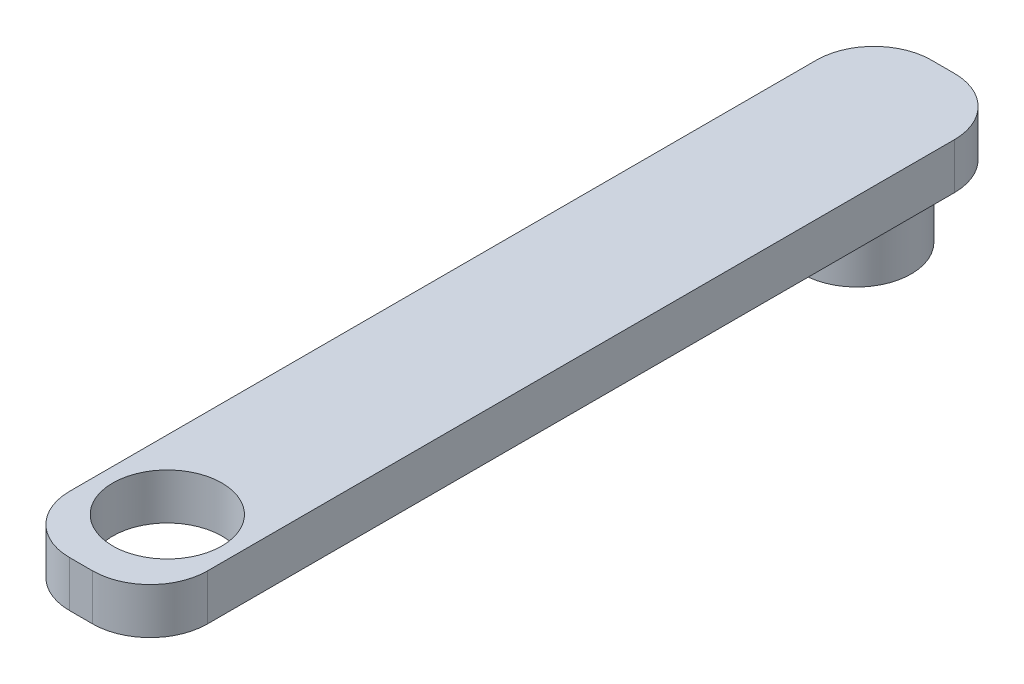
SolidWorks part; units mm, degrees
ref_plane "Front Plane" through (0, 0, 0) normal (0, 0, 1) x (1, 0, 0)
ref_plane "Top Plane" through (0, 0, 0) normal (0, 1, 0) x (1, 0, 0)
ref_plane "Right Plane" through (0, 0, 0) normal (1, 0, 0) x (0, 0, -1)
sketch "Sketch2" plane through (0, 0, 0) normal (0, 1, 0) x (1, 0, 0)
  line L0 (-55, 0) -> (55, 0) construction
  line L1 (-1, -37.5) -> (1, -37.5)
  line L2 (-6, -32.5) -> (-6, 32.5)
  line L3 (-1, 37.5) -> (1, 37.5)
  line L4 (6, -32.5) -> (6, 32.5)
  line L5 (-6, -37.5) -> (6, 37.5) construction
  line L6 (-6, 37.5) -> (6, -37.5) construction
  arc A0 (-1, -37.5) -> (-6, -32.5) centre (-1, -32.5) cw
  arc A1 (-1, 37.5) -> (-6, 32.5) centre (-1, 32.5) ccw
  arc A2 (1, -37.5) -> (6, -32.5) centre (1, -32.5) ccw
  arc A3 (6, 32.5) -> (1, 37.5) centre (1, 32.5) ccw
  circle A4 centre (0, 30) radius 4.75
  circle A5 centre (0, -30) radius 4.75
  point P0 (0, 0)
  dimension "D3" = 5
  dimension "D4" = 9.5
  dimension "D1" = 12
  dimension "D2" = 75
  dimension "D5" = 30
  dimension "D6" = 60
extrude "Boss-Extrude1" add sketch "Sketch2" along normal blind 4 contours L4 A3 L3 A1 L2 A0 L1 A2
extrude "Boss-Extrude2" add sketch "Sketch2<4>" against normal blind 5.5 contours A4 region at (0, 0, -30)
sketch "Sketch2<4>" plane through (0, 0, 0) normal (0, 1, 0) x (1, 0, 0) same geometry as "Sketch2"
extrude "Cut-Extrude1" cut sketch "Sketch2<5>" along normal up to surface (4 mm away) contours A5 up to face at (0, 4, 0)
sketch "Sketch2<5>" plane through (0, 0, 0) normal (0, 1, 0) x (1, 0, 0) same geometry as "Sketch2"
